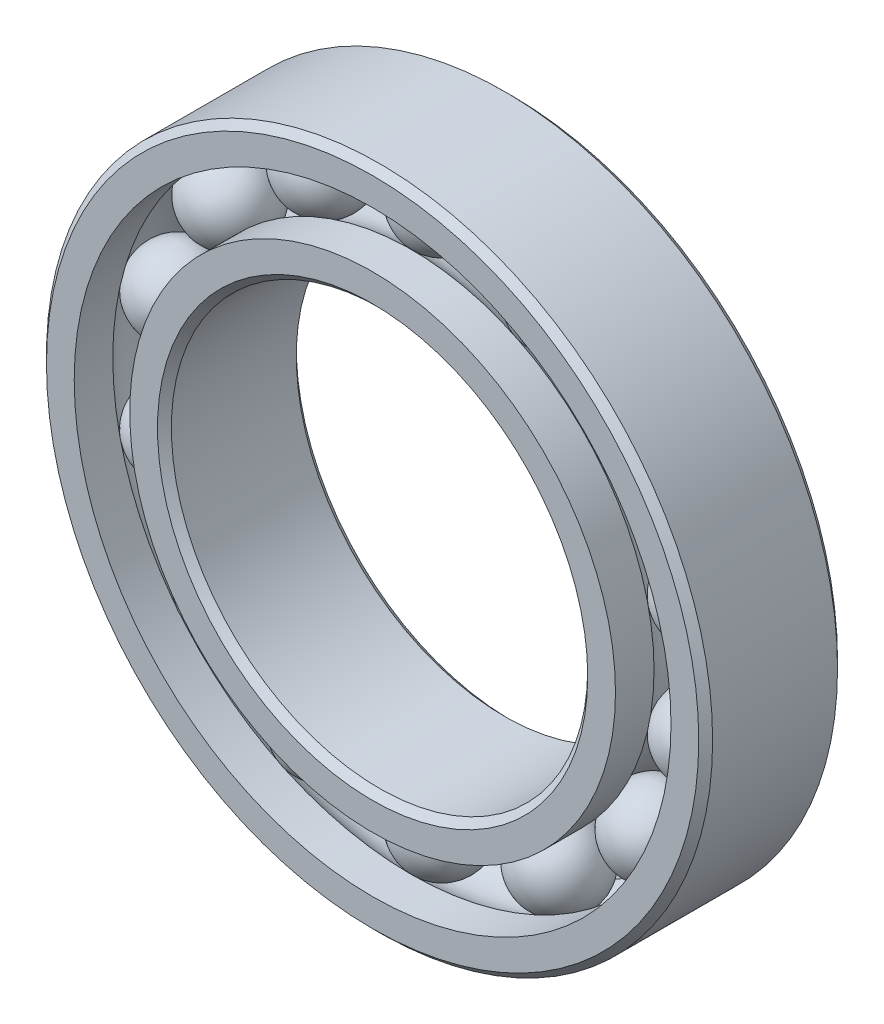
SolidWorks part; units mm, degrees
ref_plane "Front Plane" through (0, 0, 0) normal (0, 0, 1) x (1, 0, 0)
ref_plane "Top Plane" through (0, 0, 0) normal (0, 1, 0) x (1, 0, 0)
ref_plane "Right Plane" through (0, 0, 0) normal (1, 0, 0) x (0, 0, -1)
sketch "Sketch1" plane through (0, 0, 0) normal (0, 0, 1) x (1, 0, 0)
  circle A0 centre (0, 0) radius 12
  circle A1 centre (0, 0) radius 7.5
  dimension "OD" = 24
  dimension "ID" = 15
sketch "Sketch5" plane through (0, 0, 0) normal (1, 0, 0) x (0, 0, -1)
  line L0 (-2.5, 0) -> (2.5, 0) construction
  line L1 (0, 12) -> (0, -12) construction
  line L2 (2.25, 12) -> (-2.25, 12)
  line L3 (-2.25, 12) -> (-2.5, 11.75)
  line L4 (-2.5, 11.75) -> (-2.5, 10.75)
  line L5 (-2.5, 10.75) -> (-1.1111, 10.75)
  line L6 (2.5, 10.75) -> (1.1111, 10.75)
  line L7 (2.5, 11.75) -> (2.5, 10.75)
  line L8 (2.25, 12) -> (2.5, 11.75)
  line L9 (0, 12) -> (0, 9.75) construction
  line L10 (0, 9.75) -> (0, 7.5) construction
  line L11 (-1.4948, 9.75) -> (-2.5, 9.75) construction
  line L12 (1.8069, 8.7754) -> (2.1879, 8.7754) construction
  line L13 (-1.8069, 8.7754) -> (-2.1879, 8.7754) construction
  line L14 (-1.8069, 8.7754) -> (-1.8069, 10.7246) construction
  line L15 (-1.8069, 10.7246) -> (-2.1879, 10.7246) construction
  line L16 (-2.1879, 8.7754) -> (-2.1879, 10.7246) construction
  line L17 (-1.8069, 8.7754) -> (-2.1879, 10.7246) construction
  line L18 (-1.8069, 10.7246) -> (-2.1879, 8.7754) construction
  line L19 (2.1879, 8.7754) -> (2.1879, 10.7246) construction
  line L20 (1.8069, 10.7246) -> (2.1879, 10.7246) construction
  line L21 (1.8069, 8.7754) -> (1.8069, 10.7246) construction
  line L22 (0, 12) -> (0, -12) construction
  arc A0 (-1.1111, 10.75) -> (1.1111, 10.75) centre (0, 9.75) cw
  circle A1 centre (0, 9.75) radius 1.4948 construction
  point P14 (0, 7.5)
  point P15 (-1.9974, 9.75)
  dimension "Width" = 5
  dimension "D1" = 45
  dimension "D2" = 0.25
  dimension "D3" = 2.2222
  dimension "D4" = 1
  dimension "D5" = 0.381
  dimension "D6" = 0.0254
  dimension "D7" = 5
revolve "Revolve1" add sketch "Sketch5" angle 360 about L0
sketch "Sketch3" plane through (0, 0, 0) normal (1, 0, 0) x (0, 0, -1)
  line L0 (-2.5, 8.75) -> (-1.1111, 8.75)
  line L1 (0, 12) -> (0, -12) construction
  line L2 (-2.5, 11.75) -> (-2.5, 10.75) construction
  line L3 (-2.5, 8.75) -> (-2.5, 7.75)
  line L4 (-2.25, 12) -> (-2.5, 11.75) construction
  line L5 (-2.5, 7.75) -> (-2.25, 7.5)
  line L6 (-2.25, 7.5) -> (2.25, 7.5)
  line L7 (2.25, 12) -> (2.25, -12) construction
  line L8 (2.25, 7.5) -> (2.5, 7.75)
  line L9 (2.5, -11.75) -> (2.5, 11.75) construction
  line L10 (2.5, 7.75) -> (2.5, 8.75)
  line L11 (2.5, 8.75) -> (1.1111, 8.75)
  line L13 (2.25, 12) -> (2.5, 11.75) construction
  arc A0 (1.1111, 10.75) -> (-1.1111, 10.75) centre (0, 9.75) ccw construction
  arc A1 (1.1111, 8.75) -> (-1.1111, 8.75) centre (0, 9.75) cw
revolve "Revolve3" add sketch "Sketch3" angle 360 about L0
sketch "Sketch4" plane through (0, 0, 0) normal (1, 0, 0) x (0, 0, -1)
  line L0 (-1.4948, 9.75) -> (1.4948, 9.75)
  arc A2 (-1.4948, 9.75) -> (1.4948, 9.75) centre (0, 9.75) cw
  arc A3 (1.1111, 10.75) -> (-1.1111, 10.75) centre (0, 9.75) ccw construction
revolve "Revolve4" add sketch "Sketch4" angle 360 about L0
pattern_circular "CirPattern1" count 14 every 25.714 of bodies 104
ref_axis "Center Axis 1" through (0, 0, -2.25) along (0, 0, 1)
equation "\"D2@Sketch5\" = \"Width@Sketch5\" * .05"
equation "\"D3@Sketch5\" = \"Width@Sketch5\" / 2.25"
equation "\"D4@Sketch5\"=((\"OD@Sketch1\"-\"ID@Sketch1\")/2)/4.5"
equation "\"D2@CirPattern1\" = 360/\"Balls@CirPattern1\""
